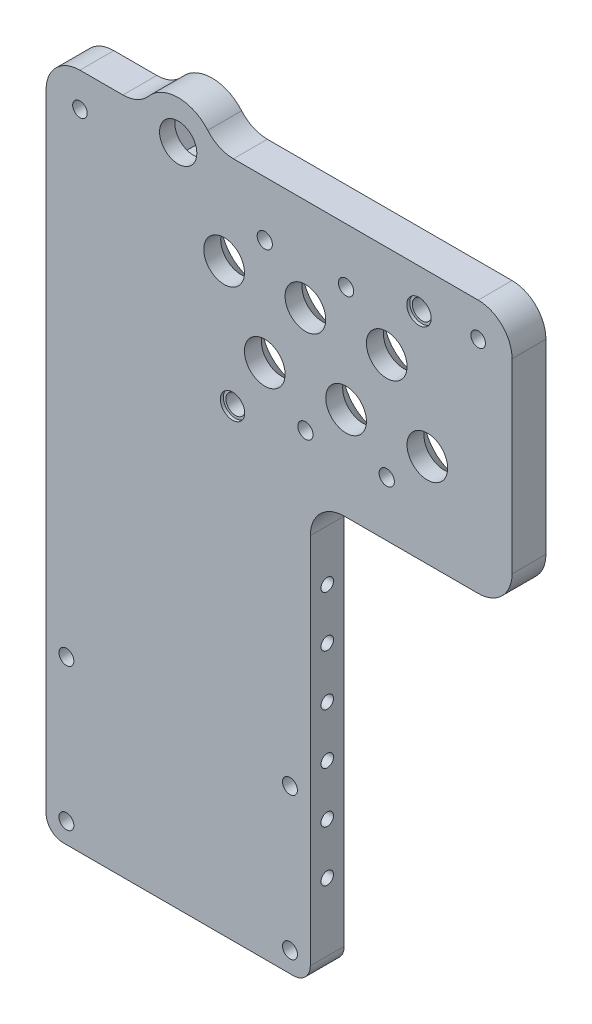
SolidWorks part; units mm, degrees
material "Petg 30% Infill"
ref_plane "Front Plane" through (0, 0, 0) normal (0, 0, 1) x (1, 0, 0)
ref_plane "Top Plane" through (0, 0, 0) normal (0, 1, 0) x (1, 0, 0)
ref_plane "Right Plane" through (0, 0, 0) normal (1, 0, 0) x (0, 0, -1)
sketch "Sketch1" plane through (0, 0, 0) normal (0, 0, 1) x (1, 0, 0)
  line L1 (-29, 200) -> (-16.3172, 200)
  line L2 (-39, 190) -> (-39, 5)
  line L3 (-34, 0) -> (34, 0)
  line L4 (39, 115) -> (39, 5)
  line L5 (98.5563, 190) -> (98.5563, 135)
  line L6 (88.5563, 125) -> (49, 125)
  line L7 (13.5563, 172.5) -> (-39, 172.5) construction
  line L8 (98.5563, 152.5) -> (73.5563, 152.5) construction
  line L10 (16.3172, 200) -> (88.5563, 200)
  circle A0 centre (16.0382, 136.6364) radius 2.85
  circle A1 centre (16.0382, 136.6364) radius 4 construction
  arc A2 (-29, 200) -> (-39, 190) centre (-29, 190) ccw
  circle A3 centre (73.5563, 152.5) radius 7.5 construction
  circle A4 centre (13.5563, 172.5) radius 7.5 construction
  arc A5 (49, 125) -> (39, 115) centre (49, 115) ccw
  arc A6 (98.5563, 135) -> (88.5563, 125) centre (88.5563, 135) cw
  arc A7 (88.5563, 200) -> (98.5563, 190) centre (88.5563, 190) cw
  circle A8 centre (71.0745, 188.3636) radius 2.85
  circle A9 centre (13.5563, 172.5) radius 6
  circle A10 centre (37.5563, 172.5) radius 6
  circle A11 centre (25.5563, 152.5) radius 6
  circle A12 centre (49.5563, 152.5) radius 6
  circle A13 centre (61.5563, 172.5) radius 6
  circle A14 centre (73.5563, 152.5) radius 6
  circle A15 centre (37.5563, 141.1752) radius 2.25
  circle A16 centre (61.5563, 141.1752) radius 2.25
  circle A17 centre (49.5563, 183.8248) radius 2.25
  circle A18 centre (25.5563, 183.8248) radius 2.25
  arc A19 (-8.7278, 203.4884) -> (-16.3172, 200) centre (-16.3172, 210) cw
  circle A20 centre (0, 196) radius 5.5
  arc A21 (8.7278, 203.4884) -> (-8.7278, 203.4884) centre (0, 196) ccw
  arc A22 (8.7278, 203.4884) -> (16.3172, 200) centre (16.3172, 210) ccw
  circle A23 centre (-33, 48) radius 2.2
  circle A24 centre (-33, 6) radius 2.2
  circle A25 centre (33, 6) radius 2.2
  circle A26 centre (33, 48) radius 2.2
  arc A27 (-39, 5) -> (-34, 0) centre (-34, 5) ccw
  arc A28 (34, 0) -> (39, 5) centre (34, 5) ccw
  point P4 (0, 0)
  point P70 (10.7819, 200)
  point P80 (-39, 0)
  point P83 (39, 0)
  dimension "D3" = 10
  dimension "D5" = 11
  dimension "D6" = 12
  dimension "D7" = 5.7
  dimension "D8" = 4.5
  dimension "D9" = 10
  dimension "D10" = 6
  dimension "D13" = 4.4
  dimension "D11" = 5
  dimension "D1" = 78
  dimension "D2" = 200
  dimension "D4" = 25
  dimension "D12" = 75
  dimension "D14" = 4
extrude "Boss-Extrude1" add sketch "Sketch1" along normal blind 10
chamfer "Chamfer1" distance 5 angle 45 6 edges at (31.5563, 152.5, 0) (55.5563, 152.5, 0) (79.5563, 152.5, 0) (67.5563, 172.5, 0) (43.5563, 172.5, 0) (19.5563, 172.5, 0)
sketch "Sketch3" plane through (0, 0, 0) normal (0, 0, -1) x (-1, 0, 0)
  circle A0 centre (-33, 48) radius 4
  circle A1 centre (-33, 6) radius 4
  circle A3 centre (33, 6) radius 4
  circle A4 centre (33, 48) radius 4
  circle A5 centre (-33, 6) radius 2.2 construction
  circle A6 centre (-33, 48) radius 2.2 construction
  circle A7 centre (33, 48) radius 2.2 construction
  circle A8 centre (33, 6) radius 2.2 construction
  dimension "D1" = 8
extrude "Cut-Extrude3" cut sketch "Sketch3" against normal blind 3 and the other way through all
sketch "Sketch4" plane through (0, 0, 0) normal (0, 0, -1) x (-1, 0, 0)
  circle A0 centre (29, 190) radius 2.15
  circle A1 centre (-88.5563, 190) radius 2.15
  arc A2 (-88.5563, 200) -> (-98.5563, 190) centre (-88.5563, 190) ccw construction
  dimension "D1" = 4.3
extrude "Cut-Extrude4" cut sketch "Sketch4" against normal up to surface (10 mm away) up to face at (24.6391, 131.3374, 10)
sketch "Sketch5" plane through (0, 0, 0) normal (0, 0, -1) x (-1, 0, 0)
  circle A0 centre (-88.5563, 190) radius 4
  circle A1 centre (29, 190) radius 4
  dimension "D1" = 8
extrude "Cut-Extrude5" cut sketch "Sketch5" against normal blind 3
sketch "Sketch6" plane through (0, 0, 10) normal (0, 0, 1) x (1, 0, 0)
  circle A0 centre (71.0745, 188.3636) radius 3.6
  circle A1 centre (16.0382, 136.6364) radius 3.6
  dimension "D1" = 7.2
extrude "Cut-Extrude6" cut sketch "Sketch6" against normal blind 0.9
sketch "Sketch7" plane through (0, 0, 0) normal (0, 0, -1) x (-1, 0, 0)
  line L1 (-4.4745, 203.75) -> (-8.9489, 196)
  line L2 (-8.9489, 196) -> (-4.4745, 188.25)
  line L3 (-4.4745, 188.25) -> (4.4745, 188.25)
  line L4 (4.4745, 188.25) -> (8.9489, 196)
  line L5 (8.9489, 196) -> (4.4745, 203.75)
  line L6 (4.4745, 203.75) -> (-4.4745, 203.75)
  circle A0 centre (0, 196) radius 7.75 construction
  arc A1 (8.7278, 203.4884) -> (-8.7278, 203.4884) centre (0, 196) ccw construction
  dimension "D1" = 15.5
extrude "Cut-Extrude7" cut sketch "Sketch7" against normal blind 5.5
sketch "Sketch8" plane through (-39, 0, 0) normal (-1, 0, 0) x (0, 0, 1)
  line L0 (10, 190) -> (0, 190) construction
  circle A0 centre (5, 175) radius 1.85
  circle A1 centre (5, 160) radius 1.85
  circle A2 centre (5, 145) radius 1.85
  circle A3 centre (5, 130) radius 1.85
  circle A4 centre (5, 115) radius 1.85
  circle A5 centre (5, 100) radius 1.85
  circle A6 centre (5, 85) radius 1.85
  circle A7 centre (5, 70) radius 1.85
  circle A8 centre (5, 55) radius 1.85
  circle A9 centre (5, 40) radius 1.85
  circle A10 centre (5, 25) radius 1.85
  point P5 (5, 190)
  dimension "D1" = 3.7
  dimension "D2" = 15
  dimension "D4" = 15
  dimension "D3" = 11
extrude "Cut-Extrude8" cut sketch "Sketch8" against normal blind 20
sketch "Sketch9" plane through (39, 0, 0) normal (1, 0, 0) x (0, 0, -1)
  line L0 (-10, 115) -> (0, 115) construction
  circle A0 centre (-5, 100) radius 1.85
  circle A1 centre (-5, 85) radius 1.85
  circle A2 centre (-5, 70) radius 1.85
  circle A3 centre (-5, 55) radius 1.85
  circle A4 centre (-5, 40) radius 1.85
  circle A5 centre (-5, 25) radius 1.85
  point P4 (-5, 115)
  dimension "D2" = 3.7
  dimension "D1" = 15
  dimension "D3" = 6
extrude "Cut-Extrude9" cut sketch "Sketch9" against normal blind 20
